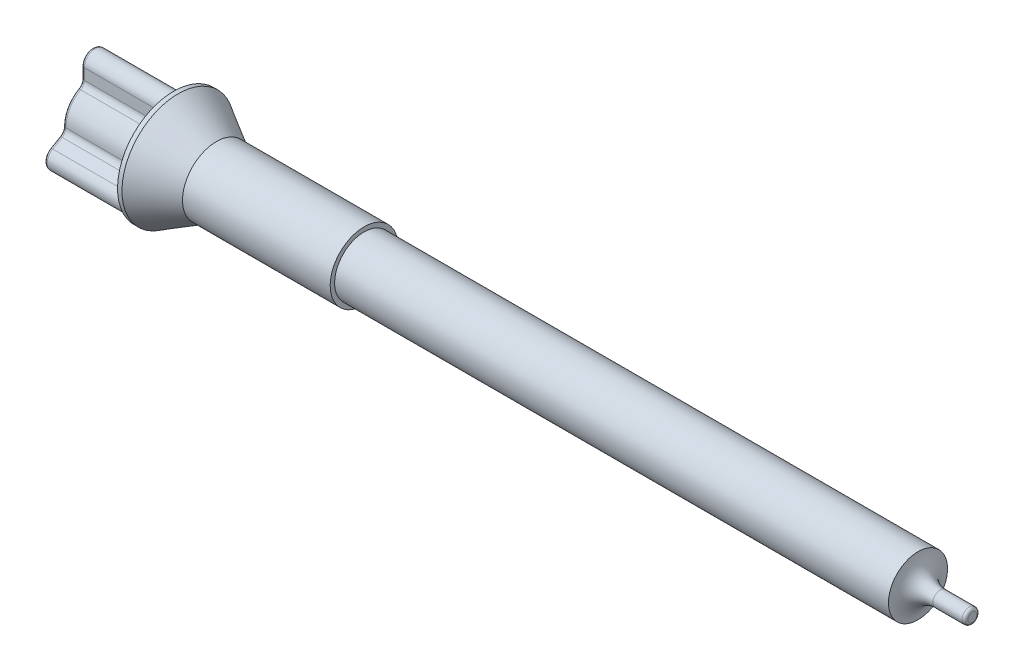
SolidWorks part; units mm, degrees
ref_plane "Front Plane" through (0, 0, 0) normal (0, 0, 1) x (1, 0, 0)
ref_plane "Top Plane" through (0, 0, 0) normal (0, 1, 0) x (1, 0, 0)
ref_plane "Right Plane" through (0, 0, 0) normal (1, 0, 0) x (0, 0, -1)
sketch "Sketch1" plane through (0, 0, 0) normal (0, 0, 1) x (1, 0, 0)
  line L0 (0, 0) -> (0, 1)
  line L1 (0, 1) -> (2.75, 1)
  line L2 (2.75, 1) -> (2.75, 1.9)
  line L3 (2.75, 1.9) -> (2.9, 1.9)
  line L4 (2.9, 1.9) -> (4.199, 1.15)
  line L5 (4.199, 1.15) -> (9.199, 1.15)
  line L6 (9.199, 1.15) -> (9.199, 1)
  line L7 (9.199, 1) -> (27.949, 1)
  line L13 (27.949, 1) -> (27.949, 0)
  line L15 (0, 0) -> (27.949, 0)
  dimension "D1" = 1
  dimension "D2" = 2.75
  dimension "D3" = 0.9
  dimension "D4" = 0.15
  dimension "D5" = 5
  dimension "D6" = 0.15
  dimension "D8" = 18.75
  dimension "D9" = 150
revolve "Revolve1" add sketch "Sketch1" angle 360 about L15
sketch "Sketch2" plane through (0, 0, 0) normal (-1, 0, 0) x (0, 0, 1)
  line L1 (-0.375, 0) -> (0.375, 0)
  line L2 (-0.375, 0) -> (-0.375, 1.45)
  line L4 (0.375, 0) -> (0.375, 1.45)
  arc A0 (-0.375, 1.45) -> (0.375, 1.45) centre (0, 1.45) cw
  point P5 (0, 0)
  dimension "D1" = 0.75
  dimension "D2" = 1.45
extrude "Boss-Extrude1" add sketch "Sketch2" against normal up to next
pattern_circular "CirPattern1" count 3 over 360 about axis through (0, 0, 0) along (-1, 0, 0) of "Boss-Extrude1" reverse direction yes
fillet "Fillet1" radius 0.25 9 edges at (1.375, -0.1388, 0.9903) (1.375, 0.927, 0.375) (1.375, -0.1388, -0.9903) (1.375, 0.927, -0.375) (1.375, -0.7883, -0.6153) (1.375, -0.7883, 0.6153) (2.75, -1, 0) (2.75, 0.5, -0.866) (2.75, 0.5, 0.866)
sketch "Sketch3" plane through (27.949, 0, 0) normal (1, 0, 0) x (0, 0, -1)
  circle A0 centre (0, 0) radius 0.25
  dimension "D1" = 0.5
extrude "Boss-Extrude2" add sketch "Sketch3" along normal blind 1.84
fillet "Fillet2" radius 0.75 1 edges at (27.949, 0.25, 0)
fillet "Fillet3" radius 0.1 19 edges at (29.789, 0.25, 0) (0, 1.825, 0) (0, 1.2663, 0.375) (0, 0.9575, 0.4085) (0, 0.5, 0.866) (0, -0.125, 1.0335) (0, -0.3084, 1.2841) (0, -0.9125, 1.5805) (0, -0.9579, 0.9091) (0, -0.8325, 0.625) (0, -1, 0) (0, -0.8325, -0.625) (0, -0.9579, -0.9091) (0, -0.9125, -1.5805) (0, -0.3084, -1.2841) (0, -0.125, -1.0335) (0, 0.5, -0.866) (0, 0.9575, -0.4085) (0, 1.2663, -0.375)
